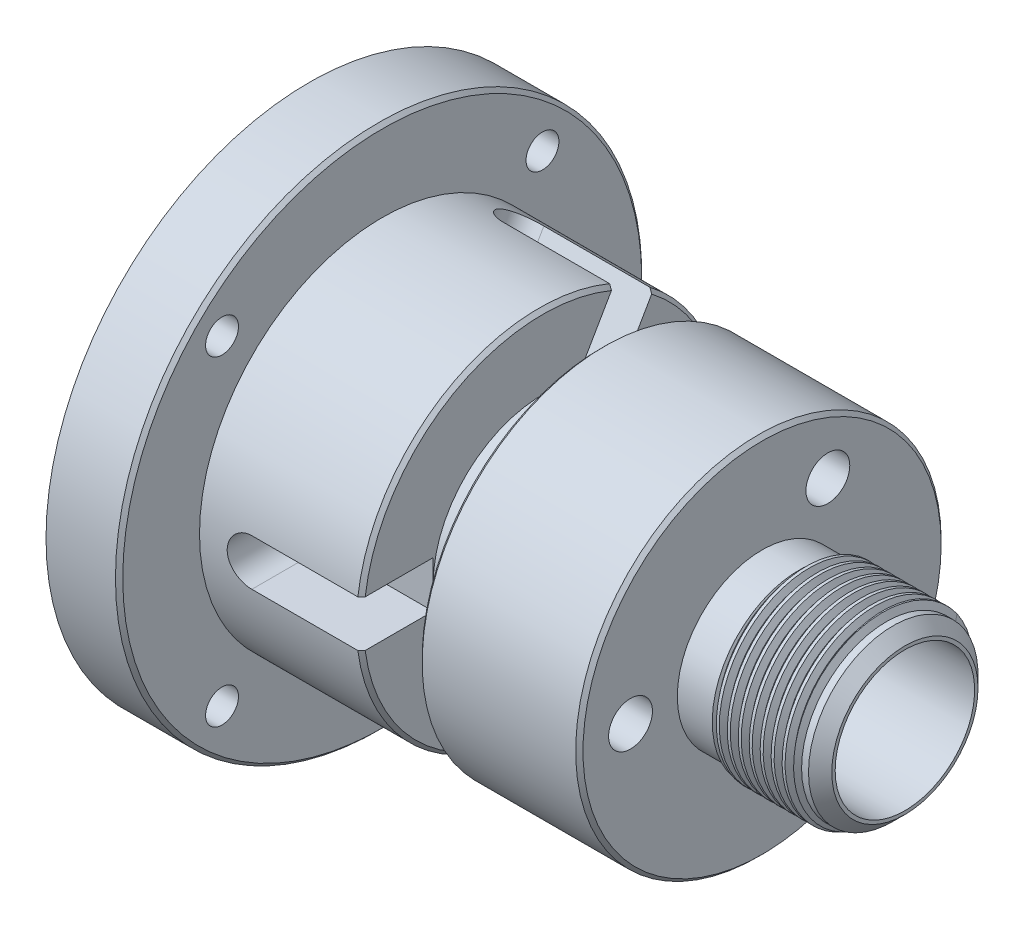
SolidWorks part; units mm, degrees
ref_plane "Front" through (0, 0, 0) normal (0, 0, 1) x (1, 0, 0)
ref_plane "Top" through (0, 0, 0) normal (0, 1, 0) x (1, 0, 0)
ref_plane "Right" through (0, 0, 0) normal (1, 0, 0) x (0, 0, -1)
sketch "Sketch1" plane through (0, 0, 0) normal (0, 0, 1) x (1, 0, 0)
  line L0 (81.5, 12.5) -> (81.5, 9.54)
  line L1 (0, 9.54) -> (81.5, 9.54)
  line L2 (0, 0) -> (73.9451, 0) construction
  line L4 (0, 12.5) -> (10, 12.5)
  line L5 (81.5, 12.5) -> (0, 12.5)
  line L6 (0, 12.5) -> (0, 9.54)
  line L7 (0, 12.5) -> (0, 36)
  line L8 (0, 36) -> (10, 36)
  line L9 (10, 12.5) -> (10, 36)
  line L10 (0, 9.54) -> (6, 9.54)
  line L11 (0, 9.54) -> (0, 22.5)
  line L12 (0, 22.5) -> (6, 22.5)
  line L13 (6, 9.54) -> (6, 22.5)
  dimension "D1" = 19.08
  dimension "D2" = 72
  dimension "D3" = 10
  dimension "D4" = 6
  dimension "D5" = 45
  dimension "D6" = 81.5
  dimension "D7" = 25
revolve "Revolve1" add sketch "Sketch1" angle 360 about L2 region at (43.75, 11.02, 0) region at (5.6857, 26.5643, 0)
sketch "Sketch2" plane through (0, 0, 0) normal (0, 1, 0) x (1, 0, 0)
  circle A0 centre (24, 0) radius 9
  dimension "D1" = 18
  dimension "D2" = 24
hole_wizard "M4 Clearance Hole1" positions "Sketch4" profile "Sketch3" hole size "M4" standard "ANSI Metric" end condition up to next
sketch "Sketch4" plane through (10, 0, 0) normal (1, 0, 0) x (0, 0, -1)
  line L1 (-21.9203, -21.9203) -> (21.9203, -21.9203)
  line L2 (-21.9203, -21.9203) -> (-21.9203, 21.9203)
  line L3 (-21.9203, 21.9203) -> (21.9203, 21.9203)
  line L4 (21.9203, -21.9203) -> (21.9203, 21.9203)
  line L5 (0, 21.9203) -> (0, -21.9203) construction
  line L6 (-21.9203, 0) -> (21.9203, 0) construction
  point P0 (-21.9203, 21.9203)
  point P2 (21.9203, 21.9203)
  point P4 (-21.9203, -21.9203)
  point P6 (21.9203, -21.9203)
  dimension "D1" = 62
sketch "Sketch3" plane through (10, 21.9203, 21.9203) normal (0, 1, 0) x (0, 0, -1)
  line L0 (0, 0) -> (0, 10)
  line L1 (0, 10) -> (2.25, 10)
  line L2 (2.25, 10) -> (2.25, 0)
  line L5 (2.25, 0) -> (0, 0)
  line L11 (0, -6.35) -> (0, 107.95) construction
  dimension "Thru Hole Dia." = 4.5
  dimension "Thru Hole Depth" = 10
chamfer "Chamfer1" distance 2.5 angle 45 1 edges at (81.5, 0, 12.5)
sketch "Sketch5" plane through (0, 0, 0) normal (0, 0, 1) x (1, 0, 0)
  line L0 (0, 0) -> (81.96, 0) construction
  line L1 (81.96, -9.54) -> (81.96, 9.54) construction
  line L2 (81.96, 12.5) -> (81.96, 11.595)
  line L3 (81.96, 11.595) -> (78.96, 11.595)
  line L4 (78.96, 11.595) -> (78.4635, 12.455)
  line L5 (78.4635, 12.455) -> (67.4565, 12.455)
  line L6 (67.4565, 12.455) -> (66.96, 11.595)
  line L7 (66.96, 11.595) -> (61.96, 11.595)
  line L8 (61.96, 11.595) -> (61.96, 12.5)
  line L9 (79, 12.5) -> (10, 12.5) construction
  line L10 (61.96, 12.5) -> (81.96, 12.5)
  dimension "D1" = 24.91
  dimension "D2" = 23.19
  dimension "D3" = 60
  dimension "D4" = 60
  dimension "D5" = 3
  dimension "D6" = 20
  dimension "D7" = 15
revolve "Cut-Revolve1" cut sketch "Sketch5" angle 360 about L0
sketch "Sketch7" plane through (81.5, 0, 0) normal (1, 0, 0) x (0, 0, -1)
  circle A0 centre (0, 0) radius 12.5
  dimension "D1" = 25
curve "Helix/Spiral1" pitch 1.5 height 16.5 radius 12.5 centre (81.5, 0, 0) axis (-1, 0, 0) start towards (0, 1, 0)
sketch "Sketch8" plane through (0, 0, 0) normal (0, 0, 1) x (1, 0, 0)
  line L0 (81.4866, 12.48) -> (81.6756, 12.48)
  line L1 (81.6756, 12.48) -> (82.1421, 11.672)
  line L2 (82.1421, 11.672) -> (82.3311, 11.672)
  line L3 (82.3311, 11.672) -> (82.7976, 12.48)
  line L4 (82.7976, 12.48) -> (82.9866, 12.48)
  line L5 (82.9866, 12.48) -> (82.9866, 12.669)
  line L6 (82.9866, 12.669) -> (81.4866, 12.669)
  line L7 (81.4866, 12.669) -> (81.4866, 12.48)
  line L8 (82.2366, 11.672) -> (82.2366, 12.669) construction
  line L9 (61.96, 0) -> (10, 0) construction
  spline S0 degree 3 poles (81.5, 12.5) (81.469, 12.5) (81.4062, 11.8491) (81.3125, 9.0689) (81.2187, 4.9081) (81.125, 0) (81.0312, -4.9081) (80.9375, -9.0689) (80.8437, -11.8491) (80.75, -12.8254) (80.6562, -11.8491) (80.5625, -9.0689) (80.4687, -4.9081) (80.375, 0) (80.2812, 4.9081) (80.1875, 9.0689) (80.0937, 11.8491) (80, 12.8254) (79.9062, 11.8491) (79.8125, 9.0689) (79.7188, 4.9081) (79.625, 0) (79.5313, -4.9081) (79.4375, -9.0689) (79.3437, -11.8491) (79.25, -12.8254) (79.1562, -11.8491) (79.0625, -9.0689) (78.9688, -4.9081) (78.875, 0) (78.7812, 4.9081) (78.6875, 9.0689) (78.5937, 11.8491) (78.5, 12.8254) (78.4062, 11.8491) (78.3125, 9.0689) (78.2188, 4.9081) (78.125, 0) (78.0312, -4.9081) (77.9375, -9.0689) (77.8438, -11.8491) (77.75, -12.8254) (77.6562, -11.8491) (77.5625, -9.0689) (77.4688, -4.9081) (77.375, 0) (77.2812, 4.9081) (77.1875, 9.0689) (77.0938, 11.8491) (77, 12.8254) (76.9062, 11.8491) (76.8125, 9.0689) (76.7188, 4.9081) (76.625, 0) (76.5312, -4.9081) (76.4375, -9.0689) (76.3438, -11.8491) (76.25, -12.8254) (76.1562, -11.8491) (76.0625, -9.0689) (75.9687, -4.9081) (75.875, 0) (75.7812, 4.9081) (75.6875, 9.0689) (75.5938, 11.8491) (75.5, 12.8254) (75.4062, 11.8491) (75.3125, 9.0689) (75.2187, 4.9081) (75.125, 0) (75.0312, -4.9081) (74.9375, -9.0689) (74.8438, -11.8491) (74.75, -12.8254) (74.6562, -11.8491) (74.5625, -9.0689) (74.4688, -4.9081) (74.375, 0) (74.2812, 4.9081) (74.1875, 9.0689) (74.0938, 11.8491) (74, 12.8254) (73.9062, 11.8491) (73.8125, 9.0689) (73.7187, 4.9081) (73.625, 0) (73.5312, -4.9081) (73.4375, -9.0689) (73.3438, -11.8491) (73.25, -12.8254) (73.1562, -11.8491) (73.0625, -9.0689) (72.9688, -4.9081) (72.875, 0) (72.7812, 4.9081) (72.6875, 9.0689) (72.5938, 11.8491) (72.5, 12.8254) (72.4062, 11.8491) (72.3125, 9.0689) (72.2187, 4.9081) (72.125, 0) (72.0312, -4.9081) (71.9375, -9.0689) (71.8438, -11.8491) (71.75, -12.8254) (71.6562, -11.8491) (71.5625, -9.0689) (71.4688, -4.9081) (71.375, 0) (71.2812, 4.9081) (71.1875, 9.0689) (71.0938, 11.8491) (71, 12.8254) (70.9062, 11.8491) (70.8125, 9.0689) (70.7188, 4.9081) (70.625, 0) (70.5312, -4.9081) (70.4375, -9.0689) (70.3437, -11.8491) (70.25, -12.8254) (70.1562, -11.8491) (70.0625, -9.0689) (69.9688, -4.9081) (69.875, 0) (69.7812, 4.9081) (69.6875, 9.0689) (69.5938, 11.8491) (69.5, 12.8254) (69.4062, 11.8491) (69.3125, 9.0689) (69.2188, 4.9081) (69.125, 0) (69.0312, -4.9081) (68.9375, -9.0689) (68.8438, -11.8491) (68.75, -12.8254) (68.6562, -11.8491) (68.5625, -9.0689) (68.4688, -4.9081) (68.375, 0) (68.2812, 4.9081) (68.1875, 9.0689) (68.0938, 11.8491) (68, 12.8254) (67.9062, 11.8491) (67.8125, 9.0689) (67.7188, 4.9081) (67.625, 0) (67.5312, -4.9081) (67.4375, -9.0689) (67.3438, -11.8491) (67.25, -12.8254) (67.1562, -11.8491) (67.0625, -9.0689) (66.9688, -4.9081) (66.875, 0) (66.7812, 4.9081) (66.6875, 9.0689) (66.5938, 11.8491) (66.5, 12.8254) (66.4063, 11.8491) (66.3125, 9.0689) (66.2188, 4.9081) (66.125, 0) (66.0313, -4.9081) (65.9375, -9.0689) (65.8438, -11.8491) (65.75, -12.8254) (65.6563, -11.8491) (65.5625, -9.0689) (65.4688, -4.9081) (65.375, 0) (65.2813, 4.9081) (65.1875, 9.0689) (65.0938, 11.8491) (65.031, 12.5) (65, 12.5) knots 0 0 0 0 0.005682 0.011364 0.017045 0.022727 0.028409 0.034091 0.039773 0.045455 0.051136 0.056818 0.0625 0.068182 0.073864 0.079545 0.085227 0.090909 0.096591 0.102273 0.107955 0.113636 0.119318 0.125 0.130682 0.136364 0.142045 0.147727 0.153409 0.159091 0.164773 0.170455 0.176136 0.181818 0.1875 0.193182 0.198864 0.204545 0.210227 0.215909 0.221591 0.227273 0.232955 0.238636 0.244318 0.25 0.255682 0.261364 0.267045 0.272727 0.278409 0.284091 0.289773 0.295455 0.301136 0.306818 0.3125 0.318182 0.323864 0.329545 0.335227 0.340909 0.346591 0.352273 0.357955 0.363636 0.369318 0.375 0.380682 0.386364 0.392045 0.397727 0.403409 0.409091 0.414773 0.420455 0.426136 0.431818 0.4375 0.443182 0.448864 0.454545 0.460227 0.465909 0.471591 0.477273 0.482955 0.488636 0.494318 0.5 0.505682 0.511364 0.517045 0.522727 0.528409 0.534091 0.539773 0.545455 0.551136 0.556818 0.5625 0.568182 0.573864 0.579545 0.585227 0.590909 0.596591 0.602273 0.607955 0.613636 0.619318 0.625 0.630682 0.636364 0.642045 0.647727 0.653409 0.659091 0.664773 0.670455 0.676136 0.681818 0.6875 0.693182 0.698864 0.704545 0.710227 0.715909 0.721591 0.727273 0.732955 0.738636 0.744318 0.75 0.755682 0.761364 0.767045 0.772727 0.778409 0.784091 0.789773 0.795455 0.801136 0.806818 0.8125 0.818182 0.823864 0.829545 0.835227 0.840909 0.846591 0.852273 0.857955 0.863636 0.869318 0.875 0.880682 0.886364 0.892045 0.897727 0.903409 0.909091 0.914773 0.920455 0.926136 0.931818 0.9375 0.943182 0.948864 0.954545 0.960227 0.965909 0.971591 0.977273 0.982955 0.988636 0.994318 1 1 1 1 construction
  dimension "D1" = 30
  dimension "D2" = 11.672
  dimension "D3" = 1.5
  dimension "D4" = 12.48
sweep "Cut-Sweep1" cut profiles "Sketch8" path "Helix/Spiral1"
sketch "Sketch9" plane through (10, 0, 0) normal (1, 0, 0) x (0, 0, -1)
  circle A0 centre (0, 0) radius 25
  circle A1 centre (0, 0) radius 12.5
  dimension "D1" = 50
  dimension "D2" = 25
extrude "Boss-Extrude3" add sketch "Sketch9" along normal up to surface (51.96 mm away) up to face at (61.96, 0, 11.595)
sketch "Sketch12" plane through (61.96, 0, 0) normal (1, 0, 0) x (0, 0, -1)
  line L0 (9, 15.5885) -> (0, 0) construction
  line L1 (0, 0) -> (9, -15.5885) construction
  line L2 (0, 0) -> (-18, 0) construction
  line L3 (9, 15.5885) -> (-18, 0) construction
  line L4 (-18, 0) -> (9, -15.5885) construction
  line L5 (9, -15.5885) -> (9, 15.5885) construction
  circle A0 centre (9, 15.5885) radius 3
  circle A1 centre (9, -15.5885) radius 3
  circle A2 centre (-18, 0) radius 3
  dimension "D1" = 6
  dimension "D2" = 18
extrude "Cut-Extrude2" cut sketch "Sketch12" against normal blind 22
sketch "Sketch13" plane through (0, 0, 0) normal (0, 0, 1) x (1, 0, 0)
  line L0 (61.96, 25) -> (10, 25) construction
  line L1 (39.96, 25) -> (31.96, 25)
  line L2 (39.96, 25) -> (39.96, 15)
  line L3 (39.96, 15) -> (31.96, 15)
  line L4 (31.96, 25) -> (31.96, 15)
  line L5 (61.96, -25) -> (61.96, 25) construction
  line L6 (81.5, 0) -> (6, 0) construction
  dimension "D1" = 22
  dimension "D2" = 8
  dimension "D3" = 15
revolve "Cut-Revolve2" cut sketch "Sketch13" angle 360 about axis through (0, 0, 0) along (-1, 0, 0)
sketch "Sketch14" plane through (0, 0, 0) normal (0, 0, 1) x (1, 0, 0)
  line L0 (33, 0) -> (15, 0) construction
  line L1 (10, 0) -> (31.96, 0) construction
  line L2 (10, -36) -> (10, 36) construction
  line L3 (31.96, -25) -> (31.96, 25) construction
  circle A0 centre (20.98, 0) radius 9.5
  dimension "D1" = 19
extrude "Cut-Extrude3" cut sketch "Sketch14" against normal through all
ref_plane "Plane1" through (0, 0, -25) normal (0, 0, -1) x (-1, 0, 0)
hole_wizard "M6x1.0 Tapped Hole1" positions "Sketch17" profile "Sketch16" tap size "M6x1.0" standard "ANSI Metric"
sketch "Sketch17" plane through (0, 0, -25) normal (0, 0, -1) x (-1, 0, 0)
  line L0 (-61.96, 0) -> (-39.96, 0) construction
  line L1 (-61.96, 0) -> (-39.96, 0) construction
  line L2 (-61.96, 11.595) -> (-61.96, -11.595) construction
  line L3 (-39.96, -25) -> (-39.96, 25) construction
  point P0 (-50.96, 0)
sketch "Sketch16" plane through (50.96, 0, -25) normal (1, 0, 0) x (0, 1, 0)
  line L0 (0, 0) -> (0, 14.5022)
  line L1 (0, 14.5022) -> (2.5, 13)
  line L2 (2.5, 13) -> (2.5, 0)
  line L5 (2.5, 0) -> (0, 0)
  line L10 (0, 14.5022) -> (-2.5, 13) construction
  line L11 (0, -6.35) -> (0, 107.95) construction
  dimension "Tap Drill Dia." = 5
  dimension "Tap Drill Depth" = 13
  dimension "Drill Angle" = 118
cosmetic thread "Hole Thread1" parameters "D1"=11, "D2"=6
chamfer "Chamfer2" distance 0.5 angle 45 4 edges at (10, 0, 36) (31.96, 0, -25) (39.96, 0, -25) (61.96, 0, -25)
ref_plane "Plane2" through (0, 0, 0) normal (0, -0.866, 0.5) x (-1, 0, 0)
sketch "Sketch18" plane through (0, 0, 0) normal (0, -0.866, 0.5) x (-1, 0, 0)
  line L0 (-31.96, 0) -> (-16.96, 0) construction
  line L1 (-31.96, 15) -> (-31.96, -15) construction
  line L2 (-81.5, 0) -> (-6, 0) construction
  line L3 (-31.96, 3.175) -> (-16.96, 3.175)
  line L4 (-31.96, -3.175) -> (-16.96, -3.175)
  arc A0 (-31.96, 3.175) -> (-31.96, -3.175) centre (-31.96, 0) ccw
  arc A1 (-16.96, -3.175) -> (-16.96, 3.175) centre (-16.96, 0) ccw
  point P7 (-24.46, 0)
  dimension "D1" = 6.35
  dimension "D2" = 15
extrude "Cut-Extrude4" cut sketch "Sketch18" against normal through all from offset 15 offset against normal yes
pattern_circular "CirPattern1" count 3 over 360 about axis through (0, 0, 0) along (-1, 0, 0) of "Cut-Extrude4"
